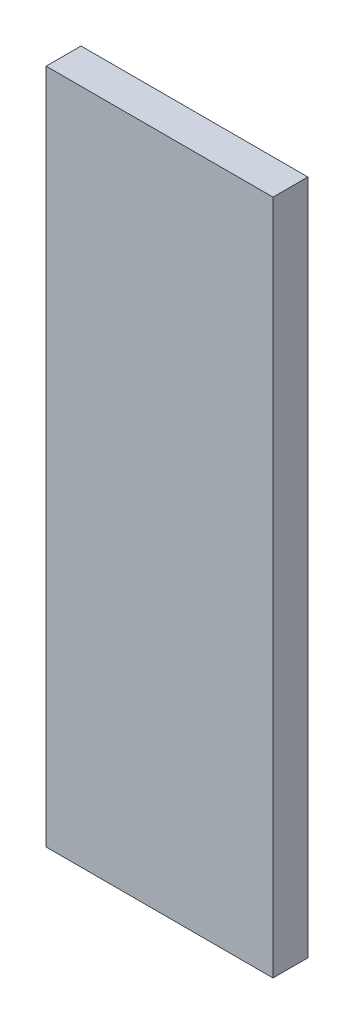
SolidWorks part; units mm, degrees
ref_plane "Front Plane" through (0, 0, 0) normal (0, 0, 1) x (1, 0, 0)
ref_plane "Top Plane" through (0, 0, 0) normal (0, 1, 0) x (1, 0, 0)
ref_plane "Right Plane" through (0, 0, 0) normal (1, 0, 0) x (0, 0, -1)
sketch "Sketch1" plane through (0, 0, 0) normal (0, 1, 0) x (1, 0, 0)
  line L0 (-13, -2) -> (13, 2) construction
  line L1 (-13, 2) -> (13, 2)
  line L2 (-13, 2) -> (-13, -2)
  line L3 (-13, -2) -> (13, -2)
  line L4 (13, 2) -> (13, -2)
  point P4 (0, 0)
  dimension "D1" = 4
  dimension "D2" = 26
extrude "Boss-Extrude1" add sketch "Sketch1" along normal blind 77.5
